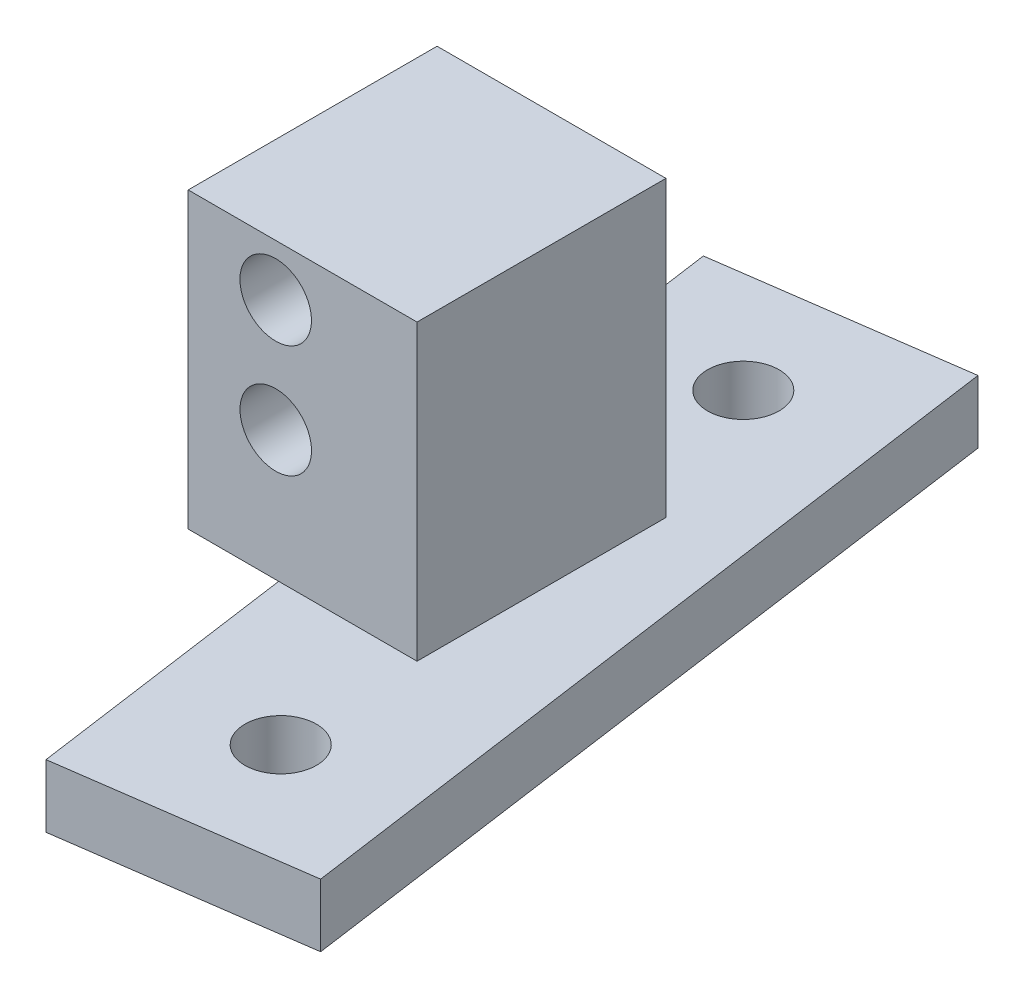
SolidWorks part; units mm, degrees
ref_plane "Front Plane" through (0, 0, 0) normal (0, 0, 1) x (1, 0, 0)
ref_plane "Top Plane" through (0, 0, 0) normal (0, 1, 0) x (1, 0, 0)
ref_plane "Right Plane" through (0, 0, 0) normal (1, 0, 0) x (0, 0, -1)
sketch "Sketch1" plane through (0, 0, 0) normal (0, 0, 1) x (1, 0, 0)
  line L0 (-111.8199, 128.5717) -> (-91.4999, 128.5717)
  line L1 (-122.8766, 128.5659) -> (-97.86, 128.5791) construction
  line L2 (-91.4999, 128.5717) -> (-91.4999, 102.49)
  line L3 (-91.4999, 102.49) -> (-111.8199, 102.49)
  line L4 (-111.8199, 102.49) -> (-111.8199, 128.5717)
  circle A0 centre (-104.0505, 124) radius 3.175
  circle A1 centre (-104.0452, 114) radius 3.175
  dimension "D4" = 6.35
  dimension "D5" = 6.35
  dimension "D1" = 20.32
  dimension "D2" = 6.35
  dimension "D3" = 3.81
extrude "Boss-Extrude1" add sketch "Sketch1" along normal up to surface (22.098 mm away)
ref_plane "Plane1" through (0, 102.49, 0) normal (0, 1, 0) x (1, 0, 0)
sketch "Sketch2" plane through (0, 102.49, 0) normal (0, 1, 0) x (1, 0, 0)
  line L0 (-109.9498, 21.7742) -> (-100.4053, -46.1384)
  line L1 (-100.4053, -46.1384) -> (-79.0254, -43.1337)
  line L2 (-79.0254, -43.1337) -> (-88.5699, 24.7789)
  line L3 (-88.5699, 24.7789) -> (-109.9498, 21.7742)
  line L4 (-111.8199, 0) -> (-91.4999, 0) construction
  circle A0 centre (-91.1294, -34.5749) radius 3.175
  circle A1 centre (-97.8459, 13.2154) radius 3.175
  dimension "D5" = 10.16
  dimension "D9" = 6.35
  dimension "D10" = 6.35
  dimension "D1" = 21.59
  dimension "D2" = 68.58
  dimension "D3" = 6.35
  dimension "D4" = 24.13
  dimension "D6" = 10.16
  dimension "D7" = 10.795
  dimension "D8" = 10.795
  dimension "D11" = 98
extrude "Boss-Extrude2" add sketch "Sketch2" against normal blind 5.588
